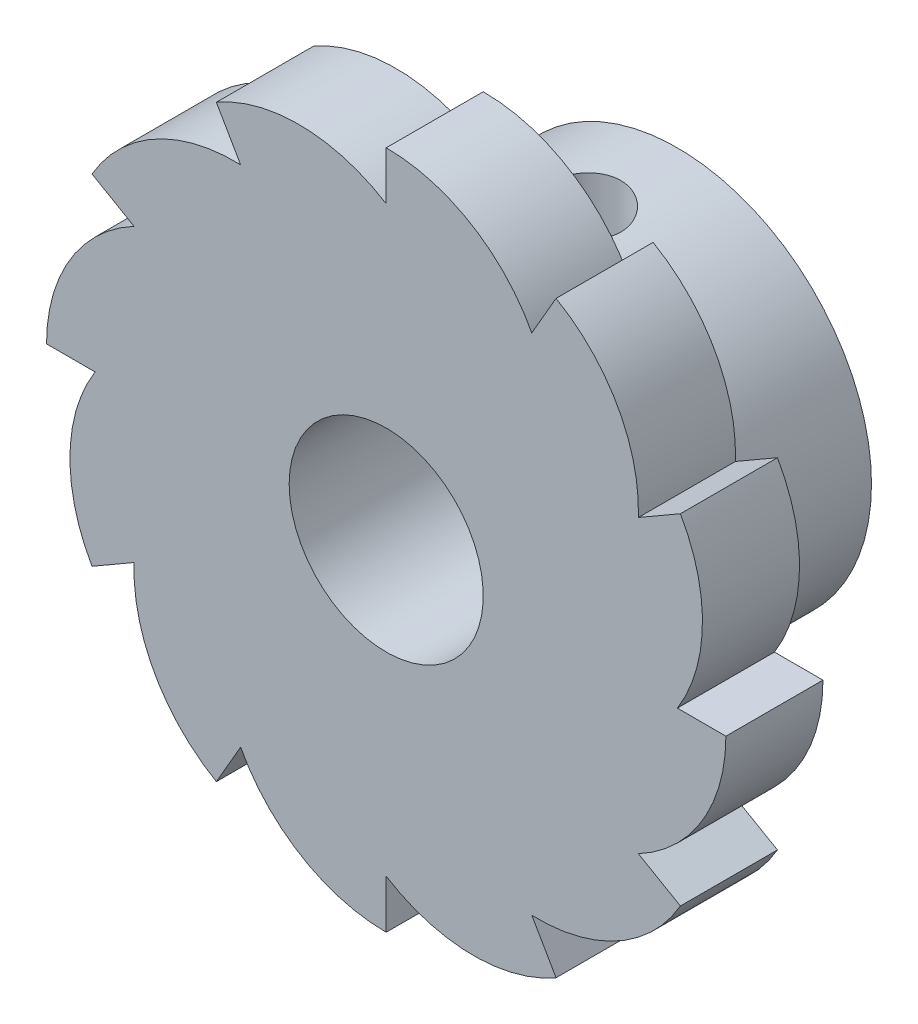
SolidWorks part; units mm, degrees
ref_plane "Front Plane" through (0, 0, 0) normal (0, 0, 1) x (1, 0, 0)
ref_plane "Top Plane" through (0, 0, 0) normal (0, 1, 0) x (1, 0, 0)
ref_plane "Right Plane" through (0, 0, 0) normal (1, 0, 0) x (0, 0, -1)
sketch "Sketch1" plane through (0, 0, 0) normal (0, 0, 1) x (1, 0, 0)
  line L0 (0, 9) -> (0, 10.5)
  line L1 (0.0027, 10.5) -> (-49999.9973, 10.5) construction
  line L2 (0, 0) -> (0, 50000) construction
  line L3 (-0.0178, -0.0309) -> (24999.9822, 43301.2393) construction
  line L4 (0, 9) -> (0, 3)
  line L5 (4.5, 7.7942) -> (1.5, 2.5981)
  circle A0 centre (0, 0) radius 9 construction
  circle A1 centre (0, 0) radius 3 construction
  arc A2 (0, 10.5) -> (4.5, 7.7942) centre (0, 5.4051) cw
  arc A3 (0, 3) -> (1.5, 2.5981) centre (0, 0) cw
  point P16 (3.6606, 8.2219)
  dimension "D1" = 6
  dimension "D2" = 18
  dimension "D3" = 30
  dimension "D4" = 1.5
extrude "Boss-Extrude1" add sketch "Sketch1" along normal blind 3
pattern_circular "CirPattern1" count 12 over 360 about axis through (0, 0, 3) along (0, 0, -1) of "Boss-Extrude1"
sketch "Sketch3" plane through (0, 0, 0) normal (0, 0, -1) x (-1, 0, 0)
  line L2 (-6, 0) -> (-6, 6)
  line L3 (-6, 6) -> (6, 6)
  line L4 (6, 0) -> (6, 6)
  circle A0 centre (0, 0) radius 6 construction
  arc A1 (6, 0) -> (-6, 0) centre (0, 0) cw
  circle A2 centre (0, 0) radius 3
  circle A3 centre (0, 0) radius 3 construction
  dimension "D1" = 12
extrude "Boss-Extrude2" add sketch "Sketch3" along normal blind 6
sketch "Sketch4" plane through (0, 6, 0) normal (0, 1, 0) x (1, 0, 0)
  line L0 (-6, 6) -> (6, 6) construction
  line L1 (-6, 6) -> (-6, 0) construction
  circle A0 centre (0, 3) radius 1.25
  point P2 (-6, 3)
  point P3 (0, 0)
  point P4 (0, 6)
  point P9 (0, 0)
  point P10 (0, 0)
  dimension "D1" = 2.5
extrude "Cut-Extrude1" cut sketch "Sketch4" against normal through all
sketch "Sketch5" plane through (0, 0, -6) normal (0, 0, -1) x (-1, 0, 0)
  line L0 (-6, 0) -> (-6, 6)
  line L1 (-6, 6) -> (6, 6)
  line L2 (6, 0) -> (6, 6) construction
  line L3 (6, 6) -> (-6, 6) construction
  line L4 (6, 6) -> (6, 0)
  arc A2 (6, 0) -> (-6, 0) centre (0, 0) ccw
  line M3 (6, 0) -> (6, 6)
  line M4 (6, 6) -> (-6, 6)
  line M5 (-6, 6) -> (-6, 0)
extrude "Cut-Extrude2" cut sketch "Sketch5" against normal up to surface (6 mm away) contours A2 L1 M5 | A2 M3 M4 region at (-4.6598, 4.6598, -6) region at (4.6598, 4.6598, -6) up to face at (0, 1.5, 0)
equation "\"ratchetTeethCount\"= 12"
equation "\"D3@Sketch1\"=360/\"ratchetTeethCount\""
equation "\"D1@CirPattern1\"=\"ratchetTeethCount\""
equation "\"ratchetHeight\"=1.5"
equation "\"D4@Sketch1\"=\"ratchetHeight\""
equation "\"ratchetInnerDiameter\"= 18"
equation "\"D2@Sketch1\"=\"ratchetInnerDiameter\""
